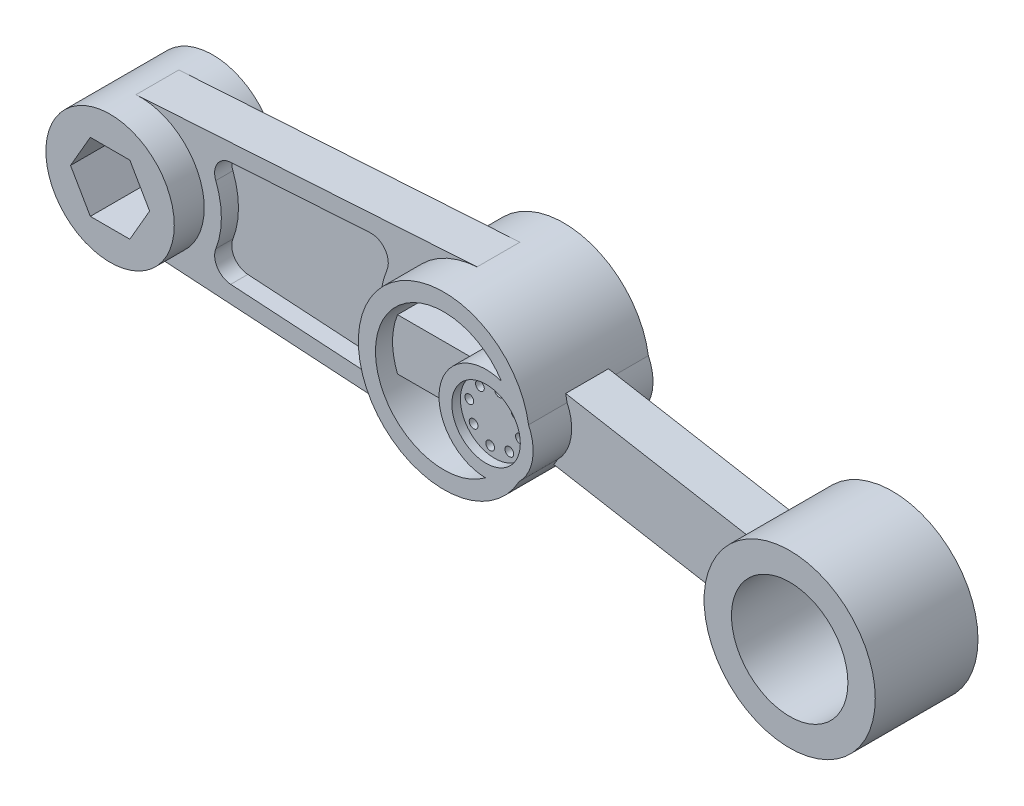
SolidWorks part; units mm, degrees
material "Copper"
ref_plane "Front Plane" through (0, 0, 0) normal (0, 0, 1) x (1, 0, 0)
ref_plane "Top Plane" through (0, 0, 0) normal (0, 1, 0) x (1, 0, 0)
ref_plane "Right Plane" through (0, 0, 0) normal (1, 0, 0) x (0, 0, -1)
ref_plane "CENTRE_Plane" through (200, 0, 0) normal (1, 0, 0) x (0, 0, -1)
ref_axis "CENTRE_Plane_Axis" through (200, 0, 38.5) along (0, 0, -1)
ref_plane "CENTRE_RIGHT_Plane" through (193.9693, -34.202, 0) normal (0.9848, -0.1736, 0) x (0, 0, -1)
ref_plane "RIGHT_Plane" through (390.9308, -68.9316, 0) normal (0.9848, -0.1736, 0) x (0, 0, -1)
sketch "Sketch1" plane through (0, 0, 0) normal (0, 0, 1) x (1, 0, 0)
  line L0 (-2.3437, 37.4267) -> (196.875, 49.9022)
  line L1 (-2.3437, -37.4267) -> (196.875, -49.9022)
  arc A0 (-2.3437, 37.4267) -> (-2.3437, -37.4267) centre (0, 0) ccw
  arc A1 (196.875, -49.9022) -> (196.875, 49.9022) centre (200, 0) ccw
  dimension "D1" = 75
  dimension "D2" = 100
extrude "LEFT_ARM" add sketch "Sketch1" along normal mid plane 25
sketch "Sketch2" plane through (0, 0, 0) normal (0, 0, 1) x (1, 0, 0)
  circle A0 centre (0, 0) radius 37.5
  dimension "D1" = 75
extrude "LEFT_Boss" add sketch "Sketch2" along normal mid plane 60
sketch "Sketch4" plane through (0, 0, 30) normal (0, 0, 1) x (1, 0, 0)
  line L0 (38.5, 0) -> (-38.5, 0) construction
  line L1 (23.094, 0) -> (11.547, 20)
  line L2 (11.547, 20) -> (-11.547, 20)
  line L3 (-11.547, 20) -> (-23.094, 0)
  line L4 (-23.094, 0) -> (-11.547, -20)
  line L5 (-11.547, -20) -> (11.547, -20)
  line L6 (11.547, -20) -> (23.094, 0)
  circle A0 centre (0, 0) radius 20 construction
  dimension "D1" = 40
extrude "LEFT_Hex" cut sketch "Sketch4" against normal through all both and the other way through all
sketch "Sketch3" plane through (0, 0, 0) normal (0, 0, 1) x (1, 0, 0)
  circle A0 centre (200, 0) radius 50
  dimension "D1" = 100
extrude "CENTRE_Boss" add sketch "Sketch3" along normal mid plane 70
sketch "Sketch5" plane through (193.9693, -34.202, 0) normal (0.9848, -0.1736, 0) x (0, 0, -1)
  line L0 (-38.5, 34.7296) -> (38.5, 34.7296) construction
  line L1 (-12.5, 14.7296) -> (12.5, 14.7296)
  line L2 (-12.5, 14.7296) -> (-12.5, 54.7296)
  line L3 (-12.5, 54.7296) -> (12.5, 54.7296)
  line L4 (12.5, 14.7296) -> (12.5, 54.7296)
  line L5 (-12.5, 14.7296) -> (12.5, 54.7296) construction
  line L6 (-12.5, 54.7296) -> (12.5, 14.7296) construction
  line L7 (0, 74.1013) -> (0, -74.1013) construction
  point P0 (0, 34.7296)
  dimension "D1" = 25
  dimension "D2" = 40
extrude "RIGHT_ARM" add sketch "Sketch5" along normal up to surface (200 mm away) up to plane "RIGHT_Plane"
sketch "RIGHT_ARM_CL" plane through (0, 0, 0) normal (0, 0, 1) x (1, 0, 0)
  line L0 (200, 0) -> (396.9616, -34.7296) construction
  line L1 (380.6614, -127.1725) -> (401.2002, -10.6908) construction
sketch "Sketch7" plane through (0, 0, 0) normal (0, 0, 1) x (1, 0, 0)
  circle A0 centre (396.9616, -34.7296) radius 50
  dimension "D1" = 100
extrude "RIGHT_Boss" add sketch "Sketch7" along normal mid plane 60
sketch "Sketch8" plane through (0, 0, 30) normal (0, 0, 1) x (1, 0, 0)
  circle A0 centre (396.9616, -34.7296) radius 34
  dimension "D1" = 68
extrude "RIGHT_Boss_Hole" cut sketch "Sketch8" against normal through all
sketch "Sketch9" plane through (0, 0, 35) normal (0, 0, 1) x (1, 0, 0)
  circle A0 centre (200, 0) radius 40
  dimension "D1" = 80
extrude "CENTRE_Hole" cut sketch "Sketch9" against normal through all
sketch "Sketch10" plane through (0, 0, 0) normal (0, 0, 1) x (1, 0, 0)
  line L0 (200, 0) -> (396.9616, -34.7296) construction
  line L1 (183.4635, -93.7829) -> (204.475, 25.3789) construction
  circle A0 centre (224.6202, -4.3412) radius 27.5
  dimension "D1" = 55
  dimension "D2" = 25
extrude "CENTRE_Blob" add sketch "Sketch10" along normal mid plane 70
sketch "Sketch11" plane through (200, 0, 0) normal (1, 0, 0) x (0, 0, -1)
  line L1 (-25, -15) -> (25, -15)
  line L2 (-25, -15) -> (-25, 15)
  line L3 (-25, 15) -> (25, 15)
  line L4 (25, -15) -> (25, 15)
  line L5 (-25, -15) -> (25, 15) construction
  line L6 (-25, 15) -> (25, -15) construction
  point P0 (0, 0)
  dimension "D1" = 50
  dimension "D2" = 30
extrude "CENTRE_Beam" add sketch "Sketch11" along normal up to next and the other way up to next
sketch "Sketch12" plane through (0, 0, 35) normal (0, 0, 1) x (1, 0, 0)
  circle A0 centre (224.6202, -4.3412) radius 20
  dimension "D1" = 40
extrude "Cut-Extrude4" cut sketch "Sketch12" against normal blind 5
hole_wizard "1/4-20 Tapped Hole1" positions "Sketch13" profile "Sketch14" tap size "1/4-20" standard "ANSI Inch" end condition up to next
sketch "Sketch13" plane through (0, 0, 30) normal (0, 0, 1) x (1, 0, 0)
  line L0 (200, 0) -> (396.9616, -34.7296) construction
  circle A0 centre (224.6202, -4.3412) radius 20 construction
  point P0 (209.8481, -1.7365)
  dimension "D1" = 15
sketch "Sketch14" plane through (209.8481, -1.7365, 30) normal (1, 0, 0) x (0, -1, 0)
  line L0 (0, 0) -> (0, 65)
  line L1 (0, 65) -> (2.5527, 65)
  line L2 (2.5527, 65) -> (2.5527, 0)
  line L5 (2.5527, 0) -> (0, 0)
  line L11 (0, -6.35) -> (0, 107.95) construction
  dimension "Thru Tap Drill Dia." = 5.1054
  dimension "Thru Tap Drill Depth" = 65
cosmetic thread "Hole Thread25" parameters "D2"=6.35
pattern_circular "CirPattern1" count 8 over 360 about axis through (224.6202, -4.3412, 30) along (0, 0, 1) of "1/4-20 Tapped Hole1"
cosmetic thread "Hole Thread26" parameters "D2"=6.35
cosmetic thread "Hole Thread27" parameters "D2"=6.35
cosmetic thread "Hole Thread28" parameters "D2"=6.35
cosmetic thread "Hole Thread29" parameters "D2"=6.35
cosmetic thread "Hole Thread30" parameters "D2"=6.35
cosmetic thread "Hole Thread31" parameters "D2"=6.35
cosmetic thread "Hole Thread32" parameters "D2"=6.35
mirror "Mirror1" about plane through (0, 0, 0) normal (0, 0, 1) of "Cut-Extrude4"
sketch "Sketch15" plane through (0, 0, 12.5) normal (0, 0, 1) x (1, 0, 0)
  line L24 (152.8661, 37.1267) -> (-1.7188, 27.4462)
  line L25 (-1.7187, -27.4462) -> (152.8661, -37.1267)
  line L26 (152.8661, 37.1267) -> (36.9354, 29.8669)
  line L27 (36.9354, -29.8669) -> (152.8661, -37.1267)
  arc A12 (152.8661, 37.1267) -> (152.8661, -37.1267) centre (200, 0) ccw
  arc A13 (152.8661, 37.1267) -> (152.8661, -37.1267) centre (200, 0) ccw
  arc A23 (-2.9687, -47.4071) -> (-2.9687, 47.4071) centre (0, 0) ccw
  arc A24 (36.9354, -29.8669) -> (36.9354, 29.8669) centre (0, 0) ccw
  dimension "D1" = 10
  dimension "D2" = 10
extrude "Cut_OUT" cut sketch "Sketch15" against normal blind 10
fillet "Fillet1" radius 10 4 edges at (152.8661, 37.1267, 7.5) (152.8661, -37.1267, 7.5) (36.9354, -29.8669, 7.5) (36.9354, 29.8669, 7.5)
mirror "Mirror2" about plane through (0, 0, 0) normal (0, 0, 1) of "Fillet1", "Cut_OUT"
sketch "Sketch16" [suppressed] plane through (0, 0, 0) normal (0, 0, 1) x (1, 0, 0)
  line L0 (395.2251, -44.5777) -> (398.698, -24.8816)
  line L1 (380.6614, -127.1725) -> (401.2002, -10.6908) construction
  line L2 (398.698, -24.8816) -> (360.8814, -18.2135)
  line L3 (360.8814, -18.2135) -> (357.4085, -37.9096)
  line L4 (357.4085, -37.9096) -> (395.2251, -44.5777)
  circle A0 centre (396.9616, -34.7296) radius 34 construction
  point P4 (396.9616, -34.7296)
  dimension "D1" = 20
  dimension "D2" = 38.4
extrude "KEYWAY" [suppressed] cut sketch "Sketch16" against normal through all both and the other way through all
mirror "Mirror3" [suppressed] about plane through (390.9308, -68.9316, 0) normal (0.9848, -0.1736, 0)
equation "\"D1@Sketch2\"=\"D1@Sketch1\""
equation "\"D1@Sketch3\"=\"D2@Sketch1\""
equation "\"D2@Sketch16\"=34+4.4"
